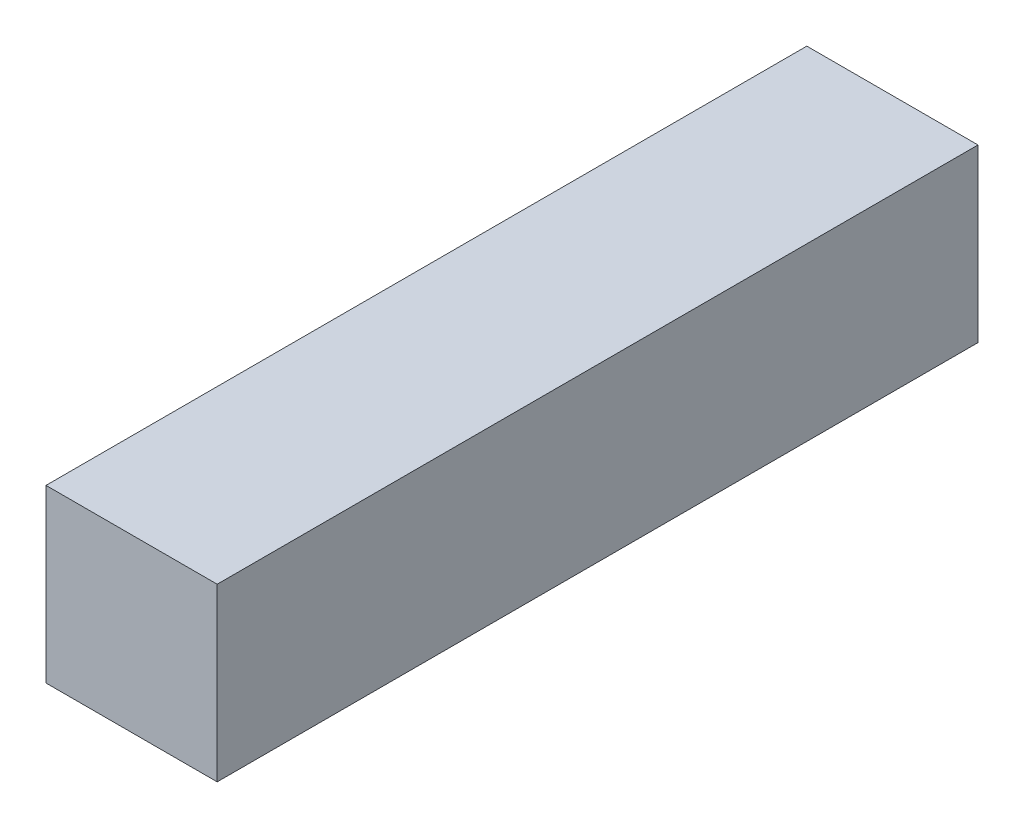
SolidWorks part; units mm, degrees
ref_plane "Front Plane" through (0, 0, 0) normal (0, 0, 1) x (1, 0, 0)
ref_plane "Top Plane" through (0, 0, 0) normal (0, 1, 0) x (1, 0, 0)
ref_plane "Right Plane" through (0, 0, 0) normal (1, 0, 0) x (0, 0, -1)
sketch "Sketch1" plane through (0, 0, 0) normal (0, 0, 1) x (1, 0, 0)
  line L1 (-2.25, -2.25) -> (2.25, -2.25)
  line L2 (-2.25, -2.25) -> (-2.25, 2.25)
  line L3 (-2.25, 2.25) -> (2.25, 2.25)
  line L4 (2.25, -2.25) -> (2.25, 2.25)
  line L5 (-2.25, -2.25) -> (2.25, 2.25) construction
  line L6 (-2.25, 2.25) -> (2.25, -2.25) construction
  point P0 (0, 0)
  dimension "D2" = 4.5
extrude "Boss-Extrude1" add sketch "Sketch1" along normal blind 20
